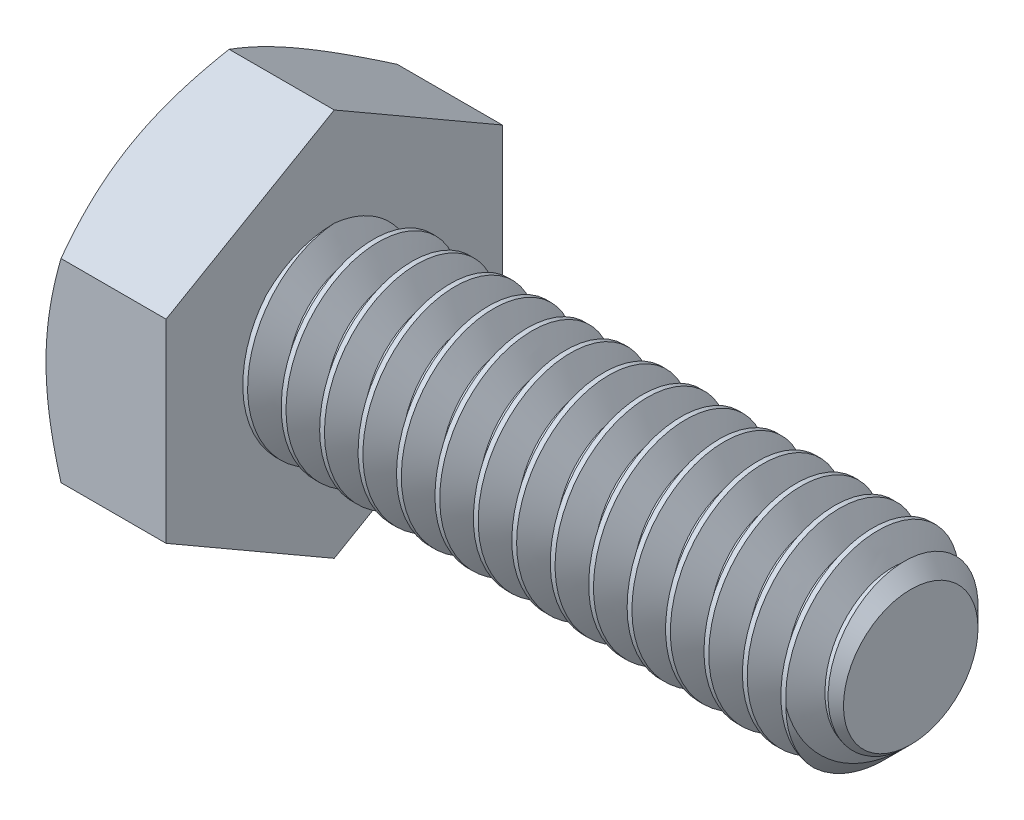
SolidWorks part; units mm, degrees
material "Wrought Stainless Steel"
ref_plane "Front Plane" through (0, 0, 0) normal (0, 0, 1) x (1, 0, 0)
ref_plane "Top Plane" through (0, 0, 0) normal (0, 1, 0) x (1, 0, 0)
ref_plane "Right Plane" through (0, 0, 0) normal (1, 0, 0) x (0, 0, -1)
sketch "Sketch1" plane through (0, 0, 0) normal (0, 0, 1) x (1, 0, 0)
  line L0 (-11.5094, 0) -> (11.5094, 0) construction
  line L1 (11.5094, 3.175) -> (11.5094, -3.175) construction
  line L2 (-7.5406, 5.5562) -> (-7.5406, -5.5562) construction
  line L3 (-11.5094, 5.5562) -> (-11.5094, -5.5562) construction
  point P9 (-7.5406, 0)
  point P10 (7.0644, -3.175)
  dimension "D1" = 4.445
  dimension "Screw Dia" = 6.35
  dimension "Hex" = 11.1125
  dimension "Head Ht" = 3.9688
  dimension "Screw Lenght" = 19.05
ref_plane "Plane2" through (11.5094, 0, 0) normal (1, 0, 0) x (0, 0, -1)
sketch "Sketch5" plane through (11.5094, 0, 0) normal (1, 0, 0) x (0, 0, -1)
  circle A0 centre (0, 0) radius 3.175
extrude "Boss-Extrude3" add sketch "Sketch5" against normal up to vertex (19.05 mm away) up to point (-7.5406, 0, 0)
sketch "Sketch9" plane through (11.5094, 0, 0) normal (1, 0, 0) x (0, 0, -1)
  circle A1 centre (0, 0) radius 3.175
  circle A2 centre (0, 0) radius 3.175
  dimension "D1" = 0
curve "Helix/Spiral1" pitch 1.27 height 20.32 turns 16 parameters "Pitch"=1.27
chamfer "Chamfer1" distance 0.9525 angle 45 1 edges at (11.5094, 0, -3.175)
sketch "Sketch10" plane through (0, 0, 0) normal (0, 0, 1) x (1, 0, 0)
  line L0 (11.5094, 3.175) -> (11.9856, 2.3501)
  line L1 (11.9856, 2.3501) -> (12.1444, 2.3501)
  line L2 (12.1444, 2.3501) -> (12.6206, 3.175)
  line L3 (11.5094, 3.175) -> (12.6206, 3.175)
  line L4 (12.065, 3.175) -> (12.065, 2.3501) construction
  line L5 (11.7475, 2.7626) -> (12.3825, 2.7626) construction
  dimension "D1" = 60
  dimension "D2" = 0.1588
  dimension "D3" = 0.635
sweep "Cut-Sweep1" cut profiles "Sketch10" path "Helix/Spiral1" align with end faces yes
sketch "Sketch6" plane through (-7.5406, 0, 0) normal (-1, 0, 0) x (0, 0, 1)
  line L0 (0, 5.5562) -> (0, -5.5562) construction
  line L1 (5.5562, 3.2079) -> (0, 6.4158)
  line L2 (0, 6.4158) -> (-5.5562, 3.2079)
  line L3 (-5.5562, 3.2079) -> (-5.5562, -3.2079)
  line L4 (-5.5562, -3.2079) -> (0, -6.4158)
  line L5 (0, -6.4158) -> (5.5562, -3.2079)
  line L6 (5.5562, -3.2079) -> (5.5562, 3.2079)
  circle A0 centre (0, 0) radius 5.5562 construction
extrude "Boss-Extrude4" add sketch "Sketch6" along normal up to vertex (3.9688 mm away) up to point (-11.5094, -5.5562, 0)
sketch "Sketch7" plane through (-11.5094, 0, 0) normal (-1, 0, 0) x (0, 0, 1)
  circle A0 centre (0, 0) radius 5.5562 construction
  circle A1 centre (0, 0) radius 5.5562
sketch "Sketch8" plane through (-11.5094, 0, 0) normal (-1, 0, 0) x (0, 0, 1)
  circle A0 centre (0, 0) radius 5.5562 construction
  circle A1 centre (0, 0) radius 5.5562
extrude "Cut-Extrude3" cut sketch "Sketch8" against normal through all draft 60 flip side to cut
equation "\"D2@Sketch10\" = \"Pitch@Helix/Spiral1\"*.125"
equation "\"D3@Sketch10\" = \"Pitch@Helix/Spiral1\"*.5"
equation "\"D3@Helix/Spiral1\" = \"Screw Lenght@Sketch1\"+\"Pitch@Helix/Spiral1\""
equation "\"D1@Chamfer1\" = \"Pitch@Helix/Spiral1\"*.75"
equation "\"D1@Sketch1\" = \"Pitch@Helix/Spiral1\"*3.5"
